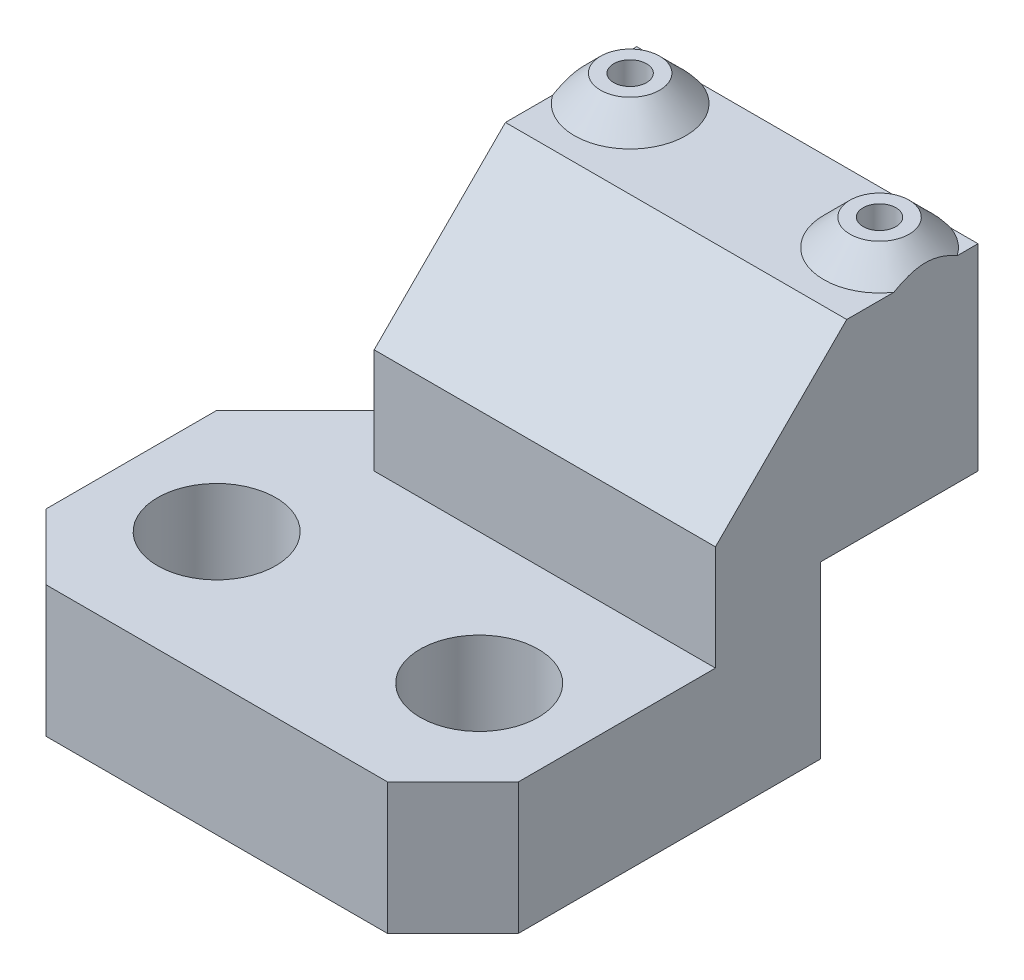
SolidWorks part; units mm, degrees
material "3D printed plastic"
ref_plane "Front Plane" through (0, 0, 0) normal (0, 0, 1) x (1, 0, 0)
ref_plane "Top Plane" through (0, 0, 0) normal (0, 1, 0) x (1, 0, 0)
ref_plane "Right Plane" through (0, 0, 0) normal (1, 0, 0) x (0, 0, -1)
sketch "Sketch1" plane through (0, 0, 0) normal (1, 0, 0) x (0, 0, -1)
  line L1 (-10, 0) -> (10, 0)
  line L2 (-10, 0) -> (-10, -18)
  line L4 (10, 0) -> (10, -15)
  line L5 (-10, -18) -> (-30, -18)
  line L7 (10, -15) -> (-2, -15)
  line L8 (-2, -28) -> (-2, -15)
  line L9 (-2, -28) -> (-30, -28)
  line L10 (-30, -18) -> (-30, -28)
  dimension "D1" = 20
  dimension "D2" = 15
  dimension "D3" = 8
  dimension "D4" = 28
  dimension "D5" = 10
  dimension "D6" = 20
extrude "Boss-Extrude1" add sketch "Sketch1" along normal mid plane 26
sketch "Sketch2" plane through (0, 0, 0) normal (0, 1, 0) x (1, 0, 0)
  line L0 (9.5, 6) -> (-9.5, 6) construction
  line L1 (0, 10) -> (0, 6) construction
  line L2 (13, 10) -> (-13, 10) construction
  circle A0 centre (-9.5, 6) radius 1.25
  circle A1 centre (9.5, 6) radius 1.25
  dimension "D1" = 19
  dimension "D2" = 2.5
  dimension "D3" = 4
extrude "Cut-Extrude1" cut sketch "Sketch2" against normal blind 12
sketch "Sketch3" plane through (0, 0, 0) normal (0, 1, 0) x (1, 0, 0)
  circle A0 centre (-9.5, 6) radius 1.25
  circle A1 centre (9.5, 6) radius 2.25
  circle A2 centre (9.5, 6) radius 1.25
  circle A3 centre (-9.5, 6) radius 2.25
  circle A4 centre (9.5, 6) radius 1.25 construction
  dimension "D1" = 4.5
extrude "Boss-Extrude2" add sketch "Sketch3" along normal blind 2
chamfer "Chamfer1" distance 2 angle 45 2 edges at (9.5, 0, -8.25) (-9.5, 0, -8.25)
sketch "Sketch5" plane through (-13, 0, 0) normal (-1, 0, 0) x (0, 0, 1)
  line L1 (2, -28) -> (30, -28)
  line L2 (2, -28) -> (2, -18)
  line L3 (2, -18) -> (30, -18)
  line L4 (30, -28) -> (30, -18)
extrude "Boss-Extrude3" add sketch "Sketch5" along normal blind 10
sketch "Sketch4" plane through (0, -18, 0) normal (0, 1, 0) x (1, 0, 0)
  line L0 (5, -20) -> (-15, -20) construction
  line L1 (13, -10) -> (13, -30) construction
  line L2 (13, -10) -> (-13, -10) construction
  circle A0 centre (-15, -20) radius 4.5
  circle A1 centre (5, -20) radius 4.5
  dimension "D1" = 9
  dimension "D2" = 8
  dimension "D3" = 20
  dimension "D4" = 10
extrude "Cut-Extrude2" cut sketch "Sketch4" against normal through all
chamfer "Chamfer2" distance 10 angle 45 1 edges at (-23, -23, 2)
chamfer "Chamfer3" distance 5 angle 45 2 edges at (13, -23, 30) (-23, -23, 30)
chamfer "Chamfer4" distance 10 angle 45 1 edges at (0, 0, 10)
